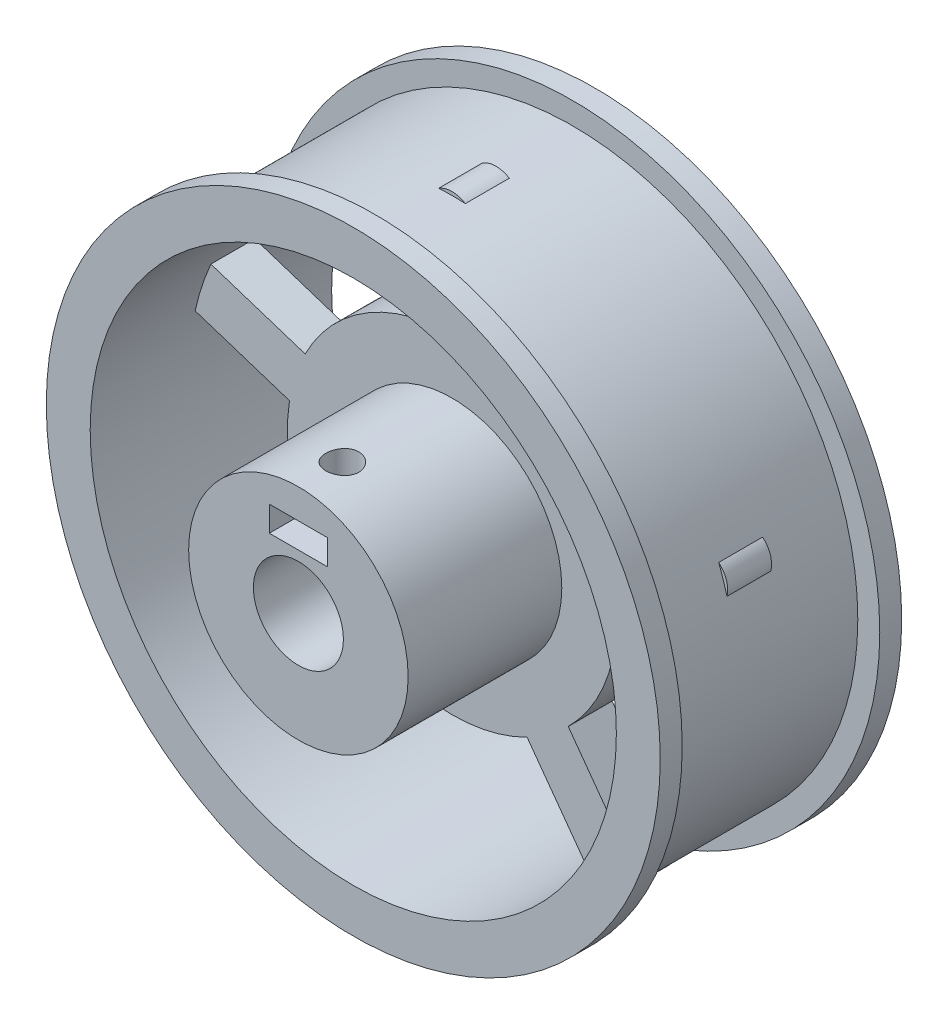
SolidWorks part; units mm, degrees
ref_plane "Front Plane" through (0, 0, 0) normal (0, 0, 1) x (1, 0, 0)
ref_plane "Top Plane" through (0, 0, 0) normal (0, 1, 0) x (1, 0, 0)
ref_plane "Right Plane" through (0, 0, 0) normal (1, 0, 0) x (0, 0, -1)
sketch "Sketch2" plane through (0, 0, 0) normal (1, 0, 0) x (0, 0, -1)
  line L0 (0, 0) -> (0, 25.9709) construction
  line L1 (-9, 25.9709) -> (9, 25.9709)
  line L2 (9, 25.9709) -> (9, 27.9709)
  line L3 (-9, 25.9709) -> (-9, 27.9709)
  line L4 (9, 27.9709) -> (11, 27.9709)
  line L5 (-9, 27.9709) -> (-11, 27.9709)
  line L6 (11, 27.9709) -> (11, 23.9709)
  line L7 (-11, 27.9709) -> (-11, 23.9709)
  line L8 (11, 23.9709) -> (-11, 23.9709)
  line L9 (-10, 0) -> (10, 0)
  point P11 (0, 23.9709)
  point P15 (0, 0)
  dimension "D1" = 18
  dimension "D2" = 2
  dimension "D3" = 2
  dimension "D4" = 4
revolve "Revolve1" add sketch "Sketch2" angle 360 about L9
sketch "Sketch3" plane through (0, 0, 0) normal (0, 0, 1) x (1, 0, 0)
  circle A0 centre (0, 0) radius 15
  circle A1 centre (0, 0) radius 4
  dimension "D1" = 30
  dimension "D2" = 8
extrude "Boss-Extrude1" add sketch "Sketch3" along normal blind 2 and the other way blind 2 separate body contours A0
sketch "Sketch6" plane through (0, 0, 0) normal (0, 0, 1) x (1, 0, 0)
  circle A0 centre (0, 0) radius 10
  dimension "D1" = 20
extrude "Boss-Extrude2" add sketch "Sketch6" along normal blind 16 and the other way blind 16
sketch "Sketch7" plane through (0, 0, 0) normal (0, 0, 1) x (1, 0, 0)
  circle A0 centre (0, 0) radius 4.1
  dimension "D1" = 8.2
extrude "Cut-Extrude6" cut sketch "Sketch7" against normal through all both and the other way through all
sketch "Sketch8" plane through (0, 0, 0) normal (0, 0, 1) x (1, 0, 0)
  line L0 (0, 11.9833) -> (0, 23.9709) construction
  line L1 (-2.315, 11.9833) -> (-2.315, 23.9709)
  line L2 (2.315, 11.9833) -> (2.315, 23.9709)
  line L3 (11.3968, 3.7031) -> (22.7977, 7.4074) construction
  line L4 (10.6815, 5.9047) -> (22.0823, 9.6091)
  line L5 (12.1122, 1.5014) -> (23.513, 5.2058)
  line L6 (7.0436, -9.6947) -> (14.0897, -19.3929) construction
  line L7 (8.9165, -8.334) -> (15.9626, -18.0322)
  line L8 (5.1708, -11.0554) -> (12.2169, -20.7536)
  line L9 (-7.0436, -9.6947) -> (-14.0897, -19.3929) construction
  line L10 (-5.1708, -11.0554) -> (-12.2169, -20.7536)
  line L11 (-8.9165, -8.334) -> (-15.9626, -18.0322)
  line L12 (-11.3968, 3.7031) -> (-22.7977, 7.4074) construction
  line L13 (-12.1122, 1.5014) -> (-23.513, 5.2058)
  line L14 (-10.6815, 5.9047) -> (-22.0823, 9.6091)
  circle A2 centre (0, 0) radius 23.9709 construction
  arc A3 (-2.315, 11.9833) -> (2.315, 11.9833) centre (0, 11.9833) ccw
  arc A4 (2.315, 23.9709) -> (-2.315, 23.9709) centre (0, 23.9709) ccw
  arc A5 (10.6815, 5.9047) -> (12.1122, 1.5014) centre (11.3968, 3.7031) ccw
  arc A6 (23.513, 5.2058) -> (22.0823, 9.6091) centre (22.7977, 7.4074) ccw
  arc A7 (8.9165, -8.334) -> (5.1708, -11.0554) centre (7.0436, -9.6947) ccw
  arc A8 (12.2169, -20.7536) -> (15.9626, -18.0322) centre (14.0897, -19.3929) ccw
  arc A9 (-5.1708, -11.0554) -> (-8.9165, -8.334) centre (-7.0436, -9.6947) ccw
  arc A10 (-15.9626, -18.0322) -> (-12.2169, -20.7536) centre (-14.0897, -19.3929) ccw
  arc A11 (-12.1122, 1.5014) -> (-10.6815, 5.9047) centre (-11.3968, 3.7031) ccw
  arc A12 (-22.0823, 9.6091) -> (-23.513, 5.2058) centre (-22.7977, 7.4074) ccw
  point P4 (0, 17.9771)
  point P14 (17.0973, 5.5552)
  point P21 (10.5667, -14.5438)
  point P28 (-10.5667, -14.5438)
  point P35 (-17.0973, 5.5552)
  point P40 (0, 0)
  dimension "D1" = 5
extrude "Boss-Extrude3" add sketch "Sketch8" along normal blind 2 and the other way blind 2
ref_plane "Plane1" through (0, 0, 12) normal (0, 0, 1) x (1, 0, 0)
sketch "Sketch10" plane through (0, 0, 12) normal (0, 0, 1) x (1, 0, 0)
  line L0 (0, 0) -> (0, 5)
  line L2 (-2.65, 5) -> (2.65, 5)
  line L3 (-2.65, 5) -> (-2.65, 7.3)
  line L4 (-2.65, 7.3) -> (2.65, 7.3)
  line L5 (2.65, 5) -> (2.65, 7.3)
  point P7 (0, 5)
  dimension "D1" = 5.3
  dimension "D2" = 2.3
extrude "Cut-Extrude7" cut sketch "Sketch10" along normal blind 4 contours L3 L4 L5 L2
sketch "Sketch11" plane through (0, 5, 0) normal (0, 1, 0) x (1, 0, 0)
  line L0 (-2.65, -12) -> (2.65, -12) construction
  circle A0 centre (0, -12) radius 1.5
  dimension "D1" = 3
extrude "Cut-Extrude8" cut sketch "Sketch11" against normal blind 4 and the other way blind 6
sketch "Sketch12" plane through (0, 5, 0) normal (0, 1, 0) x (1, 0, 0)
  line L1 (0, -15.06) -> (2.65, -13.53)
  line L2 (2.65, -13.53) -> (2.65, -10.47)
  line L3 (2.65, -10.47) -> (0, -8.94)
  line L4 (0, -8.94) -> (-2.65, -10.47)
  line L5 (-2.65, -10.47) -> (-2.65, -13.53)
  line L6 (-2.65, -13.53) -> (0, -15.06)
  circle A0 centre (0, -12) radius 2.65 construction
  point P1 (-2.65, -12)
extrude "Cut-Extrude9" cut sketch "Sketch12" along normal up to surface (2.3 mm away) up to face at (0, 7.3, 13.5833)
mirror "Mirror1" about plane through (0, 0, 0) normal (0, 0, 1) of "Cut-Extrude7", "Cut-Extrude8", "Cut-Extrude9"
